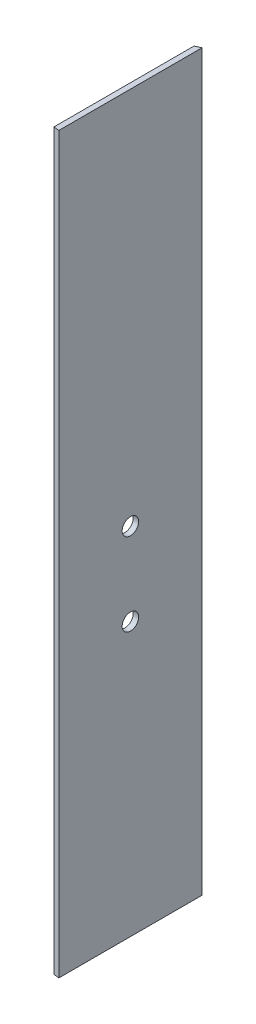
SolidWorks part; units mm, degrees
ref_plane "Спереди" through (0, 0, 0) normal (0, 0, 1) x (1, 0, 0)
ref_plane "Сверху" through (0, 0, 0) normal (0, 1, 0) x (1, 0, 0)
ref_plane "Справа" through (0, 0, 0) normal (1, 0, 0) x (0, 0, -1)
sketch "Эскиз1" plane through (0, 0, 0) normal (0, 1, 0) x (1, 0, 0)
  line L0 (1.0264, -5.5532) -> (1.0264, -107.3249)
  line L1 (1.0264, -107.3249) -> (5.0264, -107.8388)
  line L2 (5.0264, -107.8388) -> (5.0264, -3.7635)
  line L3 (5.0264, -3.7635) -> (1.0264, -5.5532)
  line L4 (0.2179, -107.1085) -> (4.8056, -108.3365) construction
  dimension "D1" = 4
extrude "Вытянуть1" add sketch "Эскиз1" along normal up to surface (533.2137 mm away)
sketch "Sketch1" plane through (5.0264, 0, 0) normal (1, 0, 0) x (0, 0, -1)
  line L0 (-55.8012, -51.361) -> (-55.8012, -149.8737) construction
  line L2 (-107.8388, 533.2137) -> (-3.7635, 533.2137) construction
  circle A0 centre (-55.8012, 258.2137) radius 6
  circle A1 centre (-55.8012, 198.2137) radius 6
  dimension "D1" = 275
  dimension "D2" = 335
extrude "Cut-Extrude1" cut sketch "Sketch1" against normal through all
